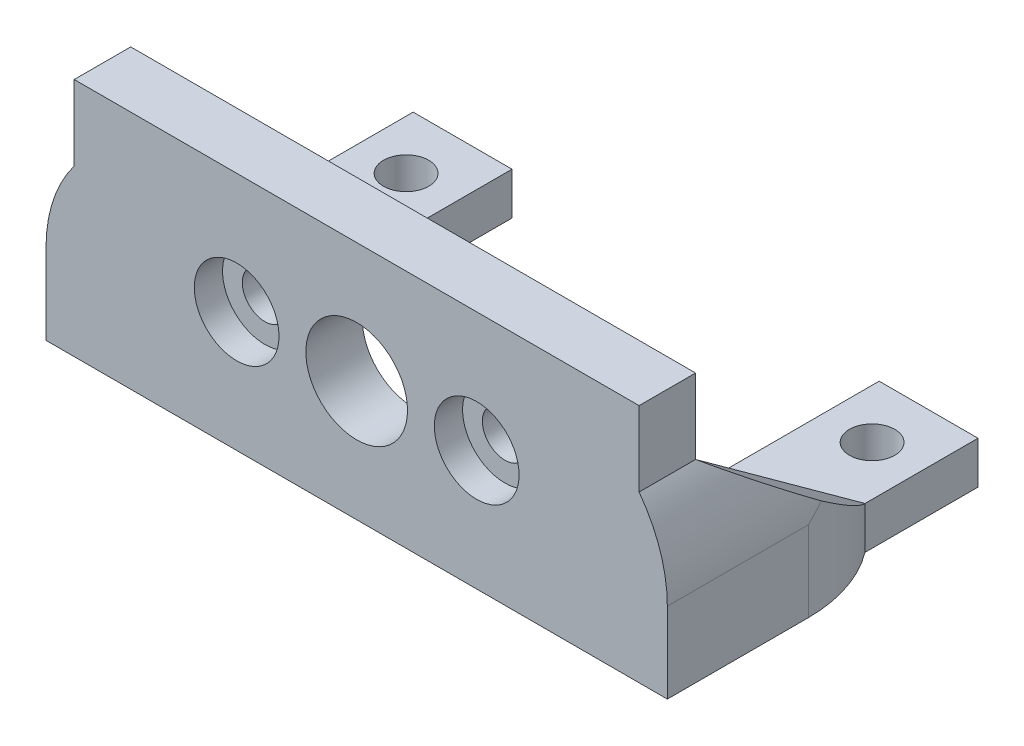
SolidWorks part; units mm, degrees
ref_plane "Front Plane" through (0, 0, 0) normal (0, 0, 1) x (1, 0, 0)
ref_plane "Top Plane" through (0, 0, 0) normal (0, 1, 0) x (1, 0, 0)
ref_plane "Right Plane" through (0, 0, 0) normal (1, 0, 0) x (0, 0, -1)
sketch "Sketch1" plane through (0, 0, 0) normal (0, 0, 1) x (1, 0, 0)
  line L0 (0, 0) -> (0, 8.0092) construction
  line L1 (-20, -8.5) -> (20, -8.5)
  line L2 (-20, -8.5) -> (-20, 8.5)
  line L3 (-20, 8.5) -> (20, 8.5)
  line L4 (20, -8.5) -> (20, 8.5)
  line L5 (-20, -8.5) -> (20, 8.5) construction
  line L6 (-20, 8.5) -> (20, -8.5) construction
  circle A0 centre (0, 0) radius 3.6
  circle A1 centre (8.5, 0) radius 1.6
  circle A2 centre (-8.5, 0) radius 1.6
  point P0 (0, 0)
  dimension "D3" = 7.2
  dimension "D4" = 3.2
  dimension "D1" = 8.5
  dimension "D2" = 40
  dimension "D5" = 8.5
extrude "Boss-Extrude1" add sketch "Sketch1" along normal blind 4
sketch "Sketch2" plane through (0, 0, 0) normal (0, 0, -1) x (-1, 0, 0)
  line L0 (20, 8.5) -> (20, -8.5) construction
  line L1 (20, -5.5) -> (13, -5.5)
  line L2 (20, -5.5) -> (20, -8.5)
  line L3 (20, -8.5) -> (13, -8.5)
  line L4 (13, -5.5) -> (13, -8.5)
  line L5 (20, -8.5) -> (-20, -8.5) construction
  dimension "D1" = 3
  dimension "D2" = 7
extrude "Boss-Extrude2" add sketch "Sketch2" along normal blind 20
sketch "Sketch3" plane through (0, -5.5, 0) normal (0, 1, 0) x (1, 0, 0)
  line L0 (-20, 0) -> (-13, 0) construction
  line L1 (-20, 20) -> (-13, 20) construction
  circle A0 centre (-16.5, 4) radius 1.5977
  circle A1 centre (-16.5, 16) radius 1.6
  point P10 (-16.5, 20)
  dimension "D1" = 3.1953
  dimension "D2" = 3.2
  dimension "D3" = 4
  dimension "D4" = 12
extrude "Cut-Extrude1" cut sketch "Sketch3" against normal blind 20
sketch "Sketch4" plane through (-20, 0, 0) normal (-1, 0, 0) x (0, 0, 1)
  line L0 (0, 3.1985) -> (-11.9986, -5.5)
  line L1 (0, 8.5) -> (0, -5.5) construction
  line L2 (-20, -5.5) -> (0, -5.5) construction
  line L3 (-11.9986, -5.5) -> (-11.9986, -8.5)
  line L4 (4, -8.5) -> (-20, -8.5) construction
  line L5 (-11.9986, -8.5) -> (4, -8.5)
  line L6 (4, -8.5) -> (4, 3.1985)
  line L7 (4, 3.1985) -> (0, 3.1985)
extrude "Boss-Extrude3" add sketch "Sketch4" along normal blind 2
fillet "Fillet1" radius 10 2 edges at (-22, -7, -11.9986) (-22, 3.1985, 2)
mirror "Mirror1" about plane through (0, 0, 0) normal (1, 0, 0) of "Fillet1", "Boss-Extrude3", "Cut-Extrude1", "Boss-Extrude2"
sketch "Sketch5" plane through (0, 0, 4) normal (0, 0, 1) x (1, 0, 0)
  circle A0 centre (-8.5, 0) radius 3
  circle A1 centre (8.5, 0) radius 3
  dimension "D1" = 6
  dimension "D2" = 6
extrude "Cut-Extrude2" cut sketch "Sketch5" against normal blind 2
